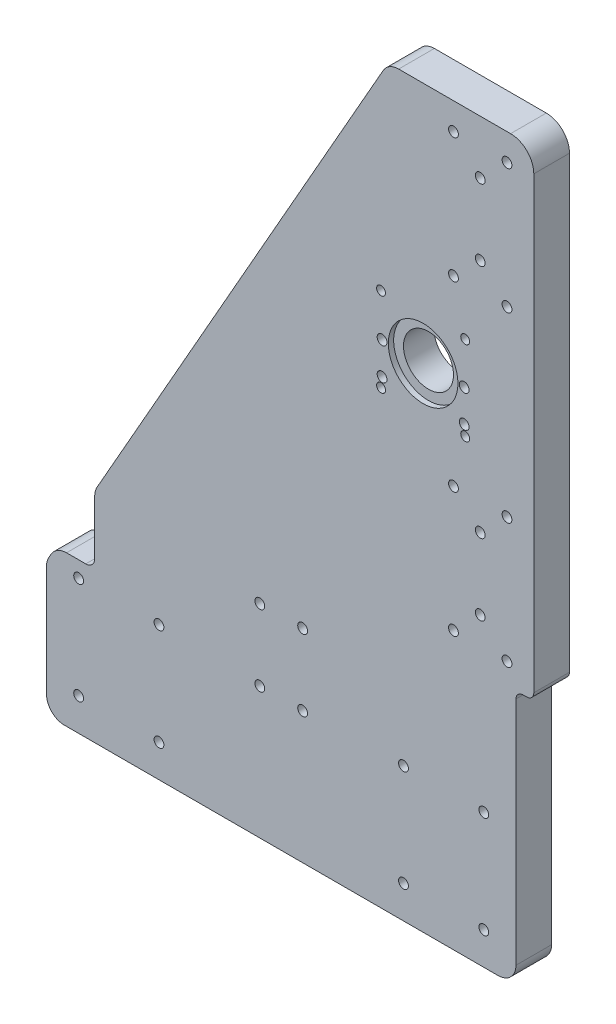
SolidWorks part; units mm, degrees
ref_plane "Front Plane" through (0, 0, 0) normal (0, 0, 1) x (1, 0, 0)
ref_plane "Top Plane" through (0, 0, 0) normal (0, 1, 0) x (1, 0, 0)
ref_plane "Right Plane" through (0, 0, 0) normal (1, 0, 0) x (0, 0, -1)
sketch "Sketch2" plane through (0, 0, 94) normal (0, 0, 1) x (1, 0, 0)
  line L1 (2186.978, 859.9095) -> (2457.8071, 859.9095)
  line L2 (2186.978, 859.9095) -> (2186.978, 457.9095)
  line L3 (2186.978, 457.9095) -> (2457.8071, 457.9095)
  line L4 (2457.8071, 859.9095) -> (2457.8071, 457.9095)
  line L6 (2441.9071, 859.9095) -> (2454.8071, 859.9095) construction
extrude "Boss-Extrude1" add sketch "Sketch2" along normal blind 20
sketch "Sketch3" plane through (0, 0, 114) normal (0, 0, 1) x (1, 0, 0)
  line L0 (2186.978, 859.9095) -> (2186.978, 457.9095) construction
  line L1 (2186.978, 864.5699) -> (2194.8071, 864.5699)
  line L2 (2186.978, 864.5699) -> (2186.978, 445.0092)
  line L3 (2186.978, 445.0092) -> (2194.8071, 445.0092)
  line L4 (2194.8071, 864.5699) -> (2194.8071, 445.0092)
extrude "Cut-Extrude1" cut sketch "Sketch3" against normal blind 20
sketch "Sketch4" plane through (0, 0, 114) normal (0, 0, 1) x (1, 0, 0)
  line L0 (2194.8071, 532.657) -> (2380.6092, 859.9095)
  line L1 (2194.8071, 457.9095) -> (2194.8071, 859.9095) construction
  line L2 (2457.8071, 859.9095) -> (2194.8071, 859.9095) construction
  line L3 (2380.6092, 859.9095) -> (2194.8071, 859.9095)
  line L4 (2194.8071, 859.9095) -> (2194.8071, 532.657)
extrude "Cut-Extrude2" cut sketch "Sketch4" against normal blind 20
fillet "Fillet1" radius 10 4 edges at (2457.8071, 457.9095, 104) (2194.8071, 457.9095, 104) (2194.8071, 532.657, 104) (2380.6092, 859.9095, 104)
hole_wizard "M5 Clearance Hole1" positions "Sketch5" profile "Sketch6" hole size "M5" standard "ISO" end condition through all
sketch "Sketch5" plane through (0, 0, 114) normal (0, 0, 1) x (1, 0, 0)
  line L5 (2212.8071, 533.1607) -> (2257.8071, 533.1607) construction
  line L6 (2257.8071, 533.1607) -> (2257.8071, 476.1607) construction
  line L7 (2257.8071, 476.1607) -> (2212.8071, 476.1607) construction
  line L8 (2212.8071, 476.1607) -> (2212.8071, 533.1607) construction
  point P0 (2212.8071, 533.1607)
  point P2 (2257.8071, 533.1607)
  point P4 (2257.8071, 476.1607)
  point P6 (2212.8071, 476.1607)
  point P23 (2439.8071, 476.1607)
  point P24 (2394.8071, 476.1607)
  point P25 (2394.8071, 533.1607)
  point P26 (2439.8071, 533.1607)
  point P85 (2338.3071, 531.6607)
  point P87 (2314.3071, 531.6607)
  point P89 (2314.3071, 571.6607)
  point P91 (2338.3071, 571.6607)
  dimension "D1" = 45
  dimension "D2" = 57
  dimension "D3" = 45
sketch "Sketch6" plane through (2212.8071, 533.1607, 114) normal (1, 0, 0) x (0, -1, 0)
  line L0 (0, 0) -> (0, 20)
  line L1 (0, 20) -> (2.75, 20)
  line L2 (2.75, 20) -> (2.75, 0)
  line L5 (2.75, 0) -> (0, 0)
  line L11 (0, -6.35) -> (0, 107.95) construction
  dimension "Thru Hole Dia." = 5.5
  dimension "Thru Hole Depth" = 20
fillet "Fillet2" radius 3 1 edges at (2457.8071, 859.9095, 104)
hole_wizard "M5 Clearance Hole2" positions "Sketch7" profile "Sketch8" hole size "M5" standard "ISO" end condition through all
sketch "Sketch7" plane through (0, 0, 114) normal (0, 0, 1) x (1, 0, 0)
  point P0 (2422.8071, 612.9095)
  point P2 (2437.8071, 627.9095)
  point P4 (2452.8071, 612.9095)
  point P6 (2452.8071, 682.9095)
  point P8 (2437.8071, 667.9095)
  point P10 (2422.8071, 682.9095)
  point P12 (2452.8071, 784.9095)
  point P14 (2422.8071, 854.9095)
  point P16 (2452.8071, 854.9095)
  point P18 (2422.8071, 784.9095)
  point P20 (2437.8071, 799.9095)
  point P22 (2437.8071, 839.9095)
sketch "Sketch8" plane through (2422.8071, 612.9095, 114) normal (1, 0, 0) x (0, -1, 0)
  line L0 (0, 0) -> (0, 20)
  line L1 (0, 20) -> (2.75, 20)
  line L2 (2.75, 20) -> (2.75, 0)
  line L5 (2.75, 0) -> (0, 0)
  line L11 (0, -6.35) -> (0, 107.95) construction
  dimension "Thru Hole Dia." = 5.5
  dimension "Thru Hole Depth" = 20
hole_wizard "M5 Clearance Hole3" positions "Sketch9" profile "Sketch10" hole size "M5" standard "ISO" end condition through all
sketch "Sketch9" plane through (0, 0, 94) normal (0, 0, -1) x (-1, 0, 0)
  point P0 (-2428.8071, 733.9095)
  point P2 (-2428.8071, 715.9095)
  point P4 (-2382.8071, 715.9095)
  point P6 (-2382.8071, 733.9095)
sketch "Sketch10" plane through (2428.8071, 733.9095, 94) normal (1, 0, 0) x (0, 1, 0)
  line L0 (0, 0) -> (0, 20)
  line L1 (0, 20) -> (2.75, 20)
  line L2 (2.75, 20) -> (2.75, 0)
  line L5 (2.75, 0) -> (0, 0)
  line L11 (0, -6.35) -> (0, 107.95) construction
  dimension "Thru Hole Dia." = 5.5
  dimension "Thru Hole Depth" = 20
sketch "Sketch11" plane through (0, 0, 114) normal (0, 0, 1) x (1, 0, 0)
  circle A3 centre (2405.8071, 733.9095) radius 19.5
  dimension "D1" = 19.5
extrude "Cut-Extrude4" cut sketch "Sketch11" against normal blind 32.2668
sketch "Sketch12" plane through (0, 0, 114) normal (0, 0, 1) x (1, 0, 0)
  line L10 (2221.8071, 542.1607) -> (2189.7804, 542.1607)
  line L11 (2221.8071, 583.4258) -> (2221.8071, 542.1607)
  line L12 (2221.8071, 583.4258) -> (2189.7804, 542.1607)
extrude "Cut-Extrude5" cut sketch "Sketch12" against normal blind 20
fillet "Fillet3" radius 10 2 edges at (2221.8071, 580.212, 104) (2200.203, 542.1607, 104)
fillet "Fillet4" radius 5 1 edges at (2221.8071, 542.1607, 104)
hole_wizard "Tap Drill for M6 Tap1" positions "Sketch13" profile "Sketch14" hole size "M6" standard "ISO" end condition through all
sketch "Sketch13" plane through (0, 0, 94) normal (0, 0, -1) x (-1, 0, 0)
  point P0 (-2429.3771, 757.4795)
  point P2 (-2382.2371, 757.4795)
  point P4 (-2429.3771, 710.3395)
  point P6 (-2382.2371, 710.3395)
sketch "Sketch14" plane through (2429.3771, 757.4795, 94) normal (1, 0, 0) x (0, 1, 0)
  line L0 (0, 0) -> (0, 20)
  line L1 (0, 20) -> (2.5, 20)
  line L2 (2.5, 20) -> (2.5, 0)
  line L5 (2.5, 0) -> (0, 0)
  line L11 (0, -6.35) -> (0, 107.95) construction
  dimension "Thru Hole Dia." = 5
  dimension "Thru Hole Depth" = 20
sketch "Sketch15" plane through (0, 0, 114) normal (0, 0, 1) x (1, 0, 0)
  line L0 (2457.8071, 467.9095) -> (2457.8071, 856.9095) construction
  line L1 (2454.8071, 859.9095) -> (2386.431, 859.9095) construction
  line L2 (2457.8071, 597.1048) -> (2457.8071, 856.9095)
  line L3 (2454.8071, 859.9095) -> (2386.431, 859.9095)
  line L4 (2467.8071, 605.1048) -> (2467.8071, 856.9095)
  line L5 (2454.8071, 869.9095) -> (2392.1086, 869.9095)
  line L6 (2463.8071, 601.1048) -> (2461.8071, 601.1048)
  line L7 (2223.111, 582.5085) -> (2377.7348, 854.8469) construction
  line L8 (2377.7348, 854.8469) -> (2383.4125, 864.8469)
  line L9 (2467.8071, 467.9095) -> (2467.8071, 856.9095) construction
  line L10 (2457.8071, 467.9095) -> (2457.8071, 856.9095) construction
  line L11 (2454.8071, 869.9095) -> (2386.431, 869.9095) construction
  line L12 (2457.8071, 597.1048) -> (2457.8071, 582.296)
  arc A0 (2386.431, 859.9095) -> (2377.7348, 854.8469) centre (2386.431, 849.9095) ccw construction
  arc A1 (2457.8071, 856.9095) -> (2454.8071, 859.9095) centre (2454.8071, 856.9095) ccw construction
  arc A2 (2386.431, 859.9095) -> (2377.7348, 854.8469) centre (2386.431, 849.9095) ccw
  arc A3 (2457.8071, 856.9095) -> (2454.8071, 859.9095) centre (2454.8071, 856.9095) ccw
  arc A4 (2467.8071, 856.9095) -> (2454.8071, 869.9095) centre (2454.8071, 856.9095) ccw
  arc A5 (2463.8071, 601.1048) -> (2467.8071, 605.1048) centre (2463.8071, 605.1048) ccw
  arc A6 (2386.431, 869.9095) -> (2369.0387, 859.7842) centre (2386.431, 849.9095) ccw construction
  arc A7 (2457.8071, 597.1048) -> (2461.8071, 601.1048) centre (2461.8071, 597.1048) cw
  arc A8 (2383.4125, 864.8469) -> (2392.1086, 869.9095) centre (2392.1086, 859.9095) cw
  line M54 (2457.8071, 467.9095) -> (2457.8071, 856.9095)
  arc M55 (2457.8071, 856.9095) -> (2454.8071, 859.9095) centre (2454.8071, 856.9095) ccw
  line M56 (2454.8071, 859.9095) -> (2386.431, 859.9095)
  arc M57 (2386.431, 859.9095) -> (2377.7348, 854.8469) centre (2386.431, 849.9095) ccw
  dimension "D2" = 4
  dimension "D3" = 10
  dimension "D1" = 10
extrude "Boss-Extrude2" add sketch "Sketch15" against normal blind 20 contours A8 L8 A7 L6 A5 L4 A4 L5 M57 M56 M55 M54 region at (2460.68, 727.0072, 114)
sketch "Sketch16" plane through (0, 0, 94) normal (0, 0, -1) x (-1, 0, 0)
  circle A0 centre (-2405.8071, 733.9095) radius 19.5 construction
  circle A1 centre (-2405.8071, 733.9095) radius 19.5
  circle A4 centre (-2405.8071, 733.9095) radius 14
  circle A5 centre (-2405.8071, 733.9095) radius 14
  dimension "D1" = 1
extrude "Boss-Extrude3" add sketch "Sketch16" against normal offset from surface (17 mm away) 3 contours A1 | A5 up to face at (2326.7058, 605.5646, 114)
